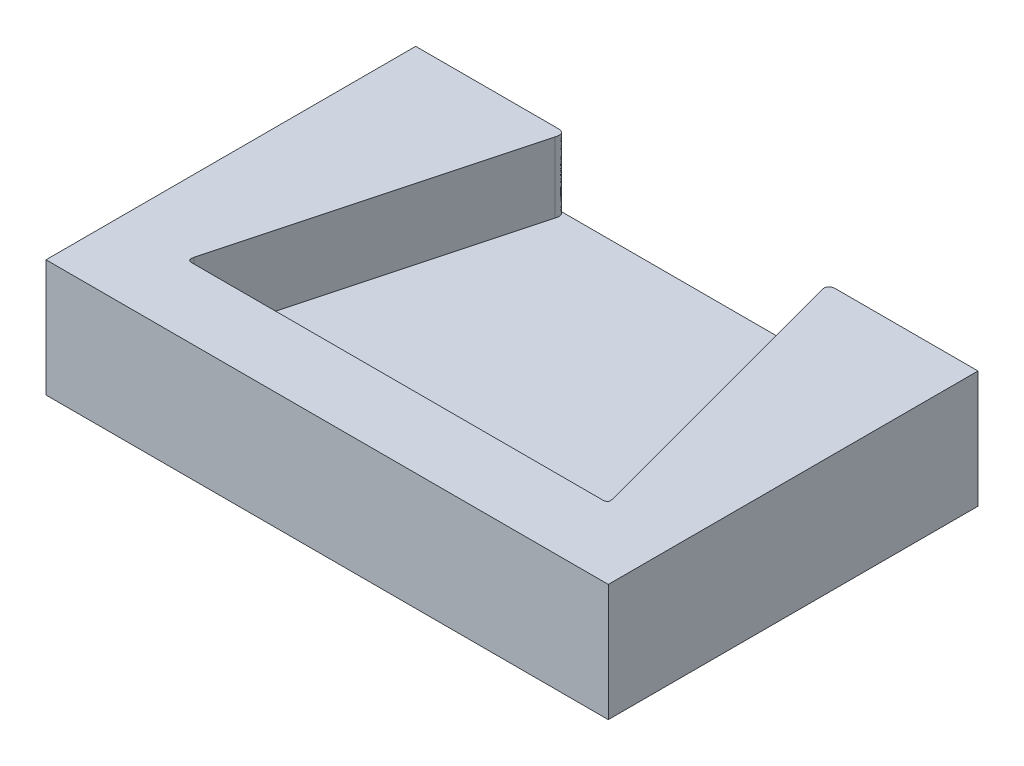
SolidWorks part; units mm, degrees
ref_plane "Front Plane" through (0, 0, 0) normal (0, 0, 1) x (1, 0, 0)
ref_plane "Top Plane" through (0, 0, 0) normal (0, 1, 0) x (1, 0, 0)
ref_plane "Right Plane" through (0, 0, 0) normal (1, 0, 0) x (0, 0, -1)
sketch "Sketch1" plane through (0, 0, 0) normal (0, 1, 0) x (1, 0, 0)
  line L1 (0, 0) -> (24, 0)
  line L2 (0, 0) -> (0, 15.78)
  line L3 (0, 15.78) -> (24, 15.78)
  line L4 (24, 0) -> (24, 15.78)
  dimension "D1" = 24
  dimension "D2" = 15.78
extrude "Boss-Extrude1" add sketch "Sketch1" along normal blind 5
sketch "Sketch2" plane through (0, 5, 0) normal (0, 1, 0) x (1, 0, 0)
  line L0 (0, 0) -> (24, 0) construction
  line L5 (24, 0) -> (24, 15.78) construction
  line L6 (6.4244, 15.78) -> (3, 3)
  line L7 (24, 15.78) -> (0, 15.78) construction
  line L8 (3, 3) -> (21, 3)
  line L9 (21, 3) -> (17.5756, 15.78)
  line L10 (17.5756, 15.78) -> (6.4244, 15.78)
  point P4 (12, 15.78)
  point P7 (12, 3)
  point P12 (12, 0)
  dimension "D1" = 3
  dimension "D2" = 75
  dimension "D3" = 3
extrude "Cut-Extrude1" cut sketch "Sketch2" against normal blind 3
fillet "Fillet1" radius 0.2 2 edges at (21, 3.5, -3) (3, 3.5, -3) curvature continuous yes
fillet "Fillet2" radius 0.3 2 edges at (6.4244, 3.5, -15.78) (17.5756, 3.5, -15.78) curvature continuous yes
